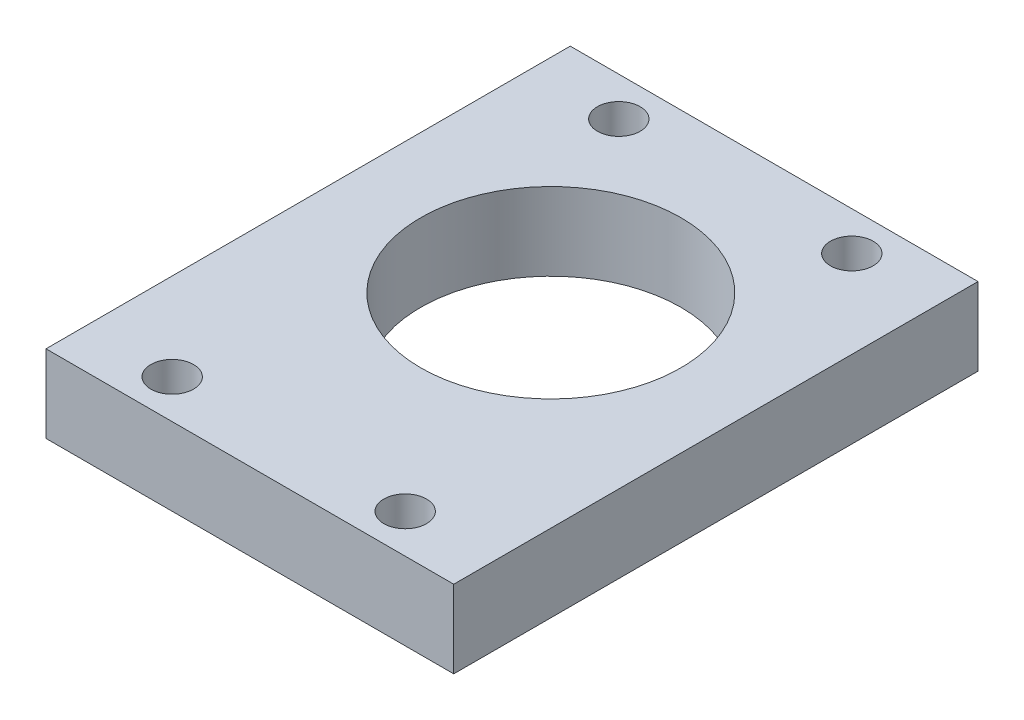
SolidWorks part; units mm, degrees
material "Alliage 1060"
ref_plane "Plan de face" through (0, 0, 0) normal (0, 0, 1) x (1, 0, 0)
ref_plane "Plan de dessus" through (0, 0, 0) normal (0, 1, 0) x (1, 0, 0)
ref_plane "Plan de droite" through (0, 0, 0) normal (1, 0, 0) x (0, 0, -1)
sketch "Esquisse1" plane through (0, 0, 0) normal (0, 1, 0) x (1, 0, 0)
  line L0 (0, 31) -> (42, 31) construction
  line L1 (0, 0) -> (42, 0)
  line L2 (0, 0) -> (0, 62)
  line L3 (0, 62) -> (42, 62)
  line L4 (42, 0) -> (42, 62)
  circle A0 centre (21, 31) radius 13.4
  point P10 (21, 31)
  dimension "D1" = 26.8
  dimension "D4" = 42
  dimension "D5" = 62
extrude "Boss.-Extru.1" add sketch "Esquisse1" along normal blind 8
sketch "Esquisse3" plane through (0, 8, 0) normal (0, 1, 0) x (1, 0, 0)
  line L0 (42, 0) -> (42, 62) construction
  line L1 (0, 62) -> (42, 62)
  line L2 (0, 62) -> (0, 54)
  line L3 (0, 54) -> (42, 54)
  line L4 (42, 62) -> (42, 54)
  dimension "D1" = 8
extrude "Enlèv. mat.-Extru.2" cut sketch "Esquisse3" against normal up to next
sketch "Esquisse2" plane through (0, 8, 0) normal (0, 1, 0) x (1, 0, 0)
  line L0 (9, 50) -> (33, 50) construction
  line L2 (0, 54) -> (0, 0) construction
  line L3 (0, 54) -> (42, 54) construction
  line L4 (21, 54) -> (21, 50) construction
  line L5 (0, 27) -> (42, 27) construction
  line L6 (42, 0) -> (42, 54) construction
  circle A0 centre (9, 50) radius 2.2
  circle A1 centre (33, 50) radius 2.2
  circle A2 centre (33, 4) radius 2.2
  circle A3 centre (9, 4) radius 2.2
  point P4 (20.1207, 55.2825)
  point P18 (0, 0)
  point P19 (0, 0)
  point P21 (21, 54)
  dimension "D1" = 4.4
  dimension "D2" = 4
  dimension "D3" = 9
extrude "Enlèv. mat.-Extru.1" cut sketch "Esquisse2" against normal through all
